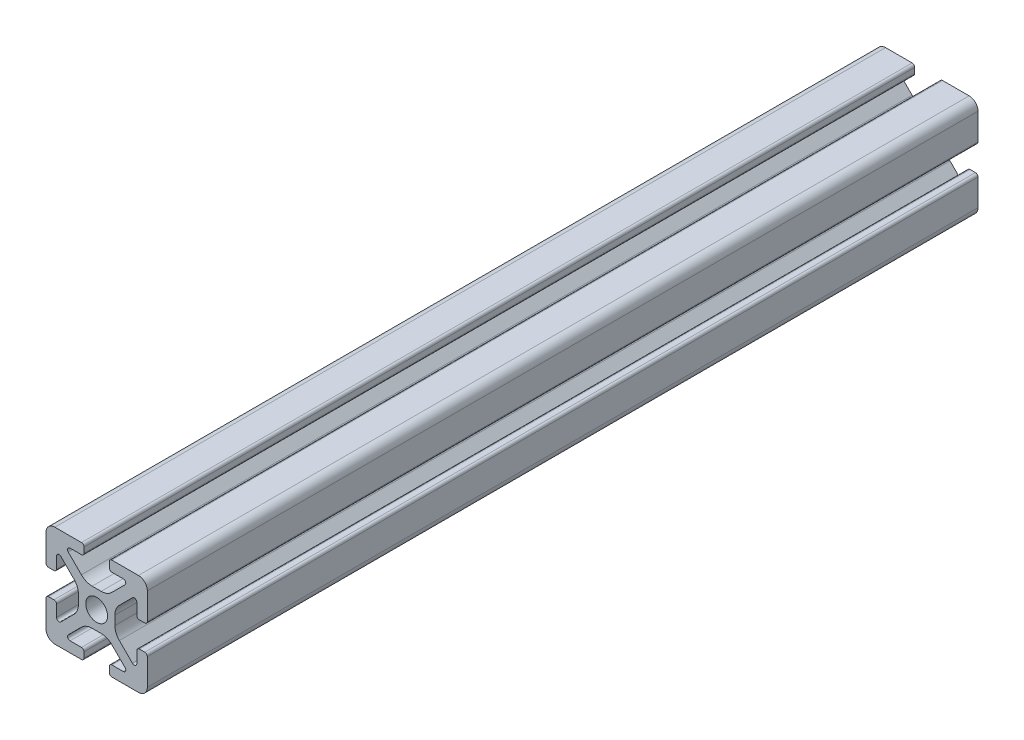
SolidWorks part; units mm, degrees
ref_plane "Front Plane" through (0, 0, 0) normal (0, 0, 1) x (1, 0, 0)
ref_plane "Top Plane" through (0, 0, 0) normal (0, 1, 0) x (1, 0, 0)
ref_plane "Right Plane" through (0, 0, 0) normal (1, 0, 0) x (0, 0, -1)
sketch "Sketch2" plane through (0, 0, 0) normal (0, 0, 1) x (1, 0, 0)
  line L0 (0, 10) -> (0, -10) construction
  line L1 (-10, 0) -> (10, 0) construction
  line L2 (2.5, -10) -> (10, -10)
  line L3 (10, -10) -> (10, -2.5)
  line L4 (2.5, -10) -> (2.5, -7.9246)
  line L5 (2.5, -7.9246) -> (6.4571, -7.9246)
  line L6 (6.4571, -7.9246) -> (2.1325, -3.6)
  line L7 (0, 0) -> (10, -10) construction
  line L8 (10, -2.5) -> (7.9246, -2.5)
  line L9 (7.9246, -2.5) -> (7.9246, -6.4571)
  line L10 (7.9246, -6.4571) -> (3.6, -2.1325)
  line L11 (5.7623, -4.2948) -> (4.2948, -5.7623) construction
  circle A0 centre (0, 0) radius 2.15
  arc A1 (5.25, -7.9246) -> (5.6036, -7.0711) centre (5.25, -7.4246) ccw construction
  point P8 (0, -3.6)
  point P16 (5.0286, -5.0286)
  dimension "Center Hole Diameter" = 4.3
  dimension "D3" = 0.5
  dimension "Rail Height" = 20
  dimension "Rail Width" = 20
  dimension "T-Slot Width" = 5
  dimension "Slot Depth" = 6.4
  dimension "Slot Inner Width" = 11.5
sketch "Sketch3" plane through (0, 0, 0) normal (1, 0, 0) x (0, 0, -1)
  line L0 (-82, -10) -> (82, -10) construction
  line L1 (-56.6, 0) -> (56.6, 0) construction
  line L2 (0, 10) -> (0, -10) construction
  line L3 (0, 10) -> (0, -10) construction
  point P6 (-56.6, 0)
  point P8 (56.6, 0)
  dimension "Length" = 164
  dimension "D1" = 25.4
sketch "Sketch4" plane through (0, 0, 0) normal (0, 0, 1) x (1, 0, 0)
  line L0 (3, -10) -> (8.25, -10)
  line L1 (2.5, -10) -> (10, -10) construction
  line L2 (2.5, -10) -> (2.5, -7.9246) construction
  line L3 (2.5, -7.9246) -> (6.4571, -7.9246) construction
  line L4 (2.5, -8.4246) -> (2.5, -9.5)
  line L5 (3, -7.9246) -> (5.25, -7.9246)
  line L6 (0, -3.6) -> (0.8898, -3.6)
  line L7 (6.4571, -7.9246) -> (2.1325, -3.6) construction
  line L8 (3.0112, -4.4787) -> (5.6036, -7.0711)
  line L9 (10, -10) -> (10, -2.5) construction
  line L10 (7.9246, -6.4571) -> (3.6, -2.1325) construction
  line L11 (7.9246, -2.5) -> (7.9246, -6.4571) construction
  line L12 (7.9246, -5.25) -> (7.9246, -3)
  line L13 (10, -2.5) -> (7.9246, -2.5) construction
  line L14 (8.4246, -2.5) -> (9.5, -2.5)
  line L15 (10, -3) -> (10, -8.25)
  line L16 (7.0711, -5.6036) -> (4.4787, -3.0112)
  line L17 (3.6, 0) -> (3.6, -0.8898)
  line L18 (-10, 0) -> (10, 0) construction
  line L19 (0, -3.6) -> (0, -2.15)
  line L20 (0, 10) -> (0, -10) construction
  line L21 (3.6, 0) -> (2.15, 0)
  arc A0 (2.5, -9.5) -> (3, -10) centre (3, -9.5) ccw
  arc A1 (5.25, -7.9246) -> (5.6036, -7.0711) centre (5.25, -7.4246) ccw construction
  arc A2 (2.5, -8.4246) -> (3, -7.9246) centre (3, -8.4246) cw
  arc A3 (5.25, -7.9246) -> (5.6036, -7.0711) centre (5.25, -7.4246) ccw
  arc A4 (0.8898, -3.6) -> (3.0112, -4.4787) centre (0.8898, -6.6) cw
  arc A5 (8.25, -10) -> (10, -8.25) centre (8.25, -8.25) ccw
  arc A6 (7.0711, -5.6036) -> (7.9246, -5.25) centre (7.4246, -5.25) ccw
  arc A7 (7.9246, -3) -> (8.4246, -2.5) centre (8.4246, -3) cw
  arc A8 (9.5, -2.5) -> (10, -3) centre (9.5, -3) cw
  arc A9 (4.4787, -3.0112) -> (3.6, -0.8898) centre (6.6, -0.8898) cw
  circle A10 centre (0, 0) radius 2.15 construction
  arc A11 (0, -2.15) -> (2.15, 0) centre (0, 0) ccw
  dimension "D1" = 1.75
  dimension "D2" = 3
extrude "Boss-Extrude1" add sketch "Sketch4" along normal mid plane 164
mirror "Mirror1" about plane through (0, 0, 0) normal (1, 0, 0) of bodies 134
mirror "Mirror2" about plane through (0, 0, 0) normal (0, 1, 0) of bodies 135
equation "\"D3@Sketch2\"=\"T-Slot Width@Sketch2\"*0.1"
equation "\"D1@Sketch4\"=\"D3@Sketch2\"*3.5"
equation "\"D2@Sketch4\"=\"D3@Sketch2\"*6"
equation "\"D1@Boss-Extrude1\"=\"Length@Sketch3\""
